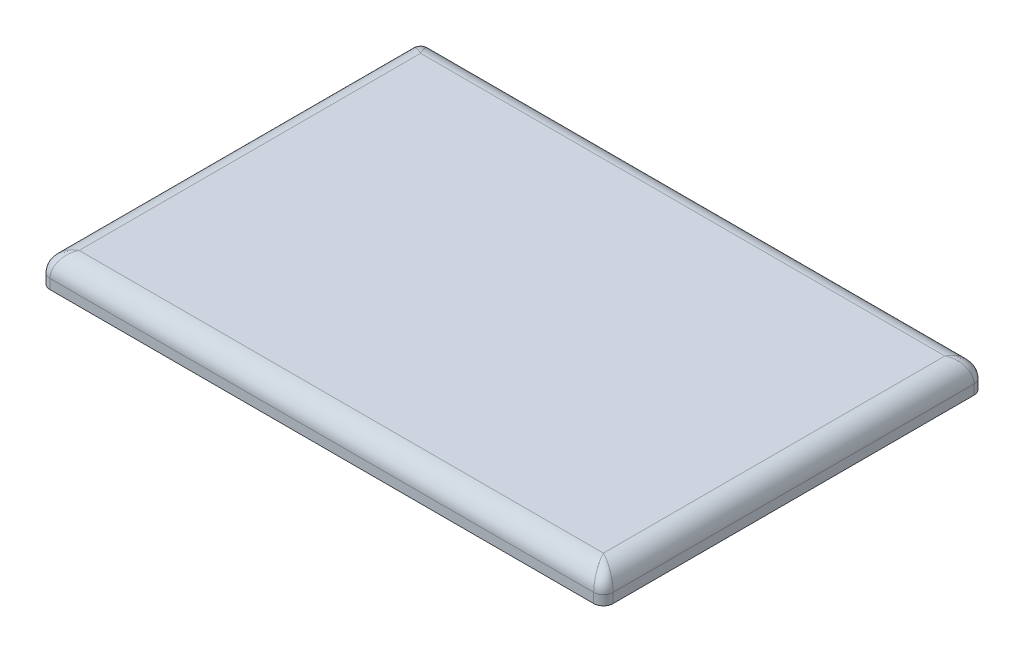
SolidWorks part; units mm, degrees
ref_plane "Front Plane" through (0, 0, 0) normal (0, 0, 1) x (1, 0, 0)
ref_plane "Top Plane" through (0, 0, 0) normal (0, 1, 0) x (1, 0, 0)
ref_plane "Right Plane" through (0, 0, 0) normal (1, 0, 0) x (0, 0, -1)
sketch "Sketch1" plane through (0, 27, 0) normal (0, 1, 0) x (1, 0, 0)
  line L0 (-27.75, -22.25) -> (-27.75, 15.4167)
  line L1 (-28.5, -23) -> (29.5, -23)
  line L2 (-28.5, -23) -> (-28.5, 16.1667)
  line L3 (-28.5, 16.1667) -> (29.5, 16.1667)
  line L4 (29.5, -23) -> (29.5, 16.1667)
  line L5 (-27.75, 15.4167) -> (28.75, 15.4167)
  line L6 (28.75, -22.25) -> (28.75, 15.4167)
  line L7 (-27.75, -22.25) -> (28.75, -22.25)
  dimension "D1" = 0.75
extrude "Boss-Extrude1" add sketch "Sketch1" along normal blind 2
sketch "Sketch2" plane through (0, 0, 22.25) normal (0, 0, -1) x (-1, 0, 0)
  line L0 (-13.75, 28) -> (12.75, 28) construction
  line L1 (-13.75, 28.4995) -> (12.75, 28.4995)
  line L2 (-13.75, 27.5005) -> (12.75, 27.5005)
  arc A0 (-13.75, 28.4995) -> (-13.75, 27.5005) centre (-13.75, 28) ccw
  arc A1 (12.75, 27.5005) -> (12.75, 28.4995) centre (12.75, 28) ccw
  point P2 (-0.5, 28)
extrude "Cut-Extrude1" cut sketch "Sketch2" against normal blind 0.5
ref_plane "Plane1" through (0, 0, 3.4167) normal (0, 0, -1) x (-1, 0, 0)
mirror "Mirror1" about plane through (0, 0, 3.4167) normal (0, 0, -1) of "Cut-Extrude1"
sketch "Sketch3" plane through (0, 29, 0) normal (0, 1, 0) x (1, 0, 0)
  line L1 (-28.5, 16.1667) -> (29.5, 16.1667)
  line L2 (-28.5, 16.1667) -> (-28.5, -23)
  line L3 (-28.5, -23) -> (29.5, -23)
  line L4 (29.5, 16.1667) -> (29.5, -23)
extrude "Boss-Extrude2" add sketch "Sketch3" along normal blind 1
fillet "Fillet1" radius 2 4 edges at (0.5, 30, 23) (-28.5, 30, 3.4167) (0.5, 30, -16.1667) (29.5, 30, 3.4167)
fillet "Fillet2" radius 1 8 edges at (28.9142, 29.4142, 22.4142) (-27.9142, 29.4142, 22.4142) (-27.9142, 29.4142, -15.5809) (28.9142, 29.4142, -15.5809) (29.5, 27.5, 23) (-28.5, 27.5, 23) (-28.5, 27.5, -16.1667) (29.5, 27.5, -16.1667)
